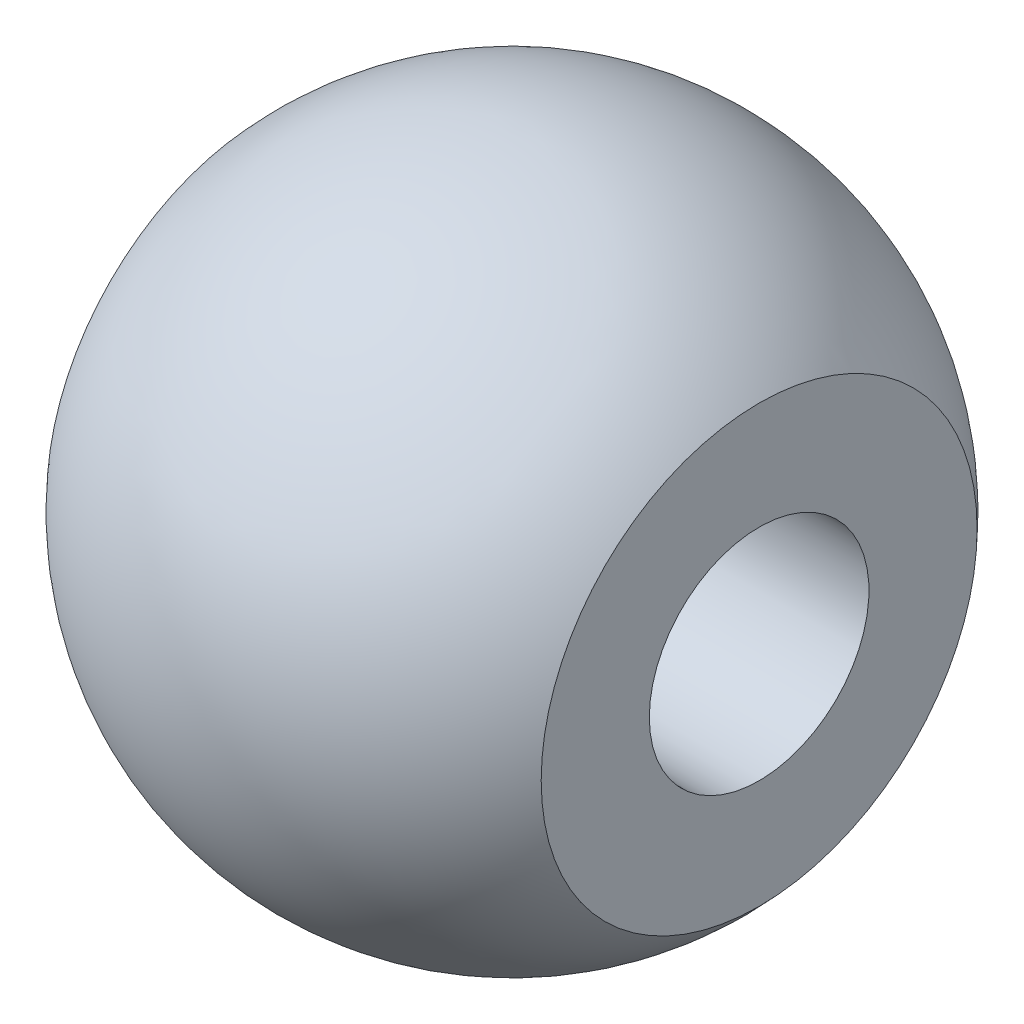
SolidWorks part; units mm, degrees
ref_plane "Front Plane" through (0, 0, 0) normal (0, 0, 1) x (1, 0, 0)
ref_plane "Top Plane" through (0, 0, 0) normal (0, 1, 0) x (1, 0, 0)
ref_plane "Right Plane" through (0, 0, 0) normal (1, 0, 0) x (0, 0, -1)
sketch "Sketch1" plane through (0, 0, 0) normal (0, 0, 1) x (1, 0, 0)
  line L0 (0, 0) -> (0, 12)
  line L1 (0, 0) -> (-0.15, 0.75)
  arc A0 (0, 12) -> (0, 0) centre (0, 6) ccw
  dimension "D1" = 12
revolve "Revolve1" add sketch "Sketch1" angle 360 about L0 region at (-2.5465, 6, 0)
sketch "Sketch3" plane through (0, 0, 0) normal (0, 1, 0) x (1, 0, 0)
  line L1 (-7.5, -7.4773) -> (-4.5, -7.4773)
  line L2 (-7.5, -7.4773) -> (-7.5, 7.4773)
  line L3 (-7.5, 7.4773) -> (-4.5, 7.4773)
  line L4 (-4.5, -7.4773) -> (-4.5, 7.4773)
  line L5 (-7.5, -7.4773) -> (-4.5, 7.4773) construction
  line L6 (-7.5, 7.4773) -> (-4.5, -7.4773) construction
  circle A0 centre (0, 0) radius 6 construction
  point P0 (-6, 0)
  dimension "D1" = 3
extrude "Cut-Extrude2" cut sketch "Sketch3" along normal up to next
mirror "Mirror2" about plane through (0, 0, 0) normal (1, 0, 0) of "Cut-Extrude2"
hole_wizard "Hole1" positions "Sketch4" profile "Sketch5" legacy
sketch "Sketch4" plane through (-4.5, 0, 0) normal (-1, 0, 0) x (0, 0, 1)
  point P0 (0, 6.0121)
sketch "Sketch5" plane through (-4.5, 6.0121, 0) normal (0, 1, 0) x (0, 0, 1)
  line L0 (0, 0) -> (0, 12)
  line L1 (0, 12) -> (2, 12)
  line L2 (2, 12) -> (2, 1.2071)
  line L3 (2, 1.2071) -> (2.5, 0)
  line L4 (2.5, 0) -> (0, 0)
  line L5 (0, -6.4453) -> (0, 115.525) construction
  line L6 (-2, 1.2071) -> (-2.5, 0) construction
  dimension "Diameter" = 4
  dimension "Depth" = 12
  dimension "C-Sink Angle" = 45
  dimension "C-Sink Diameter" = 5
